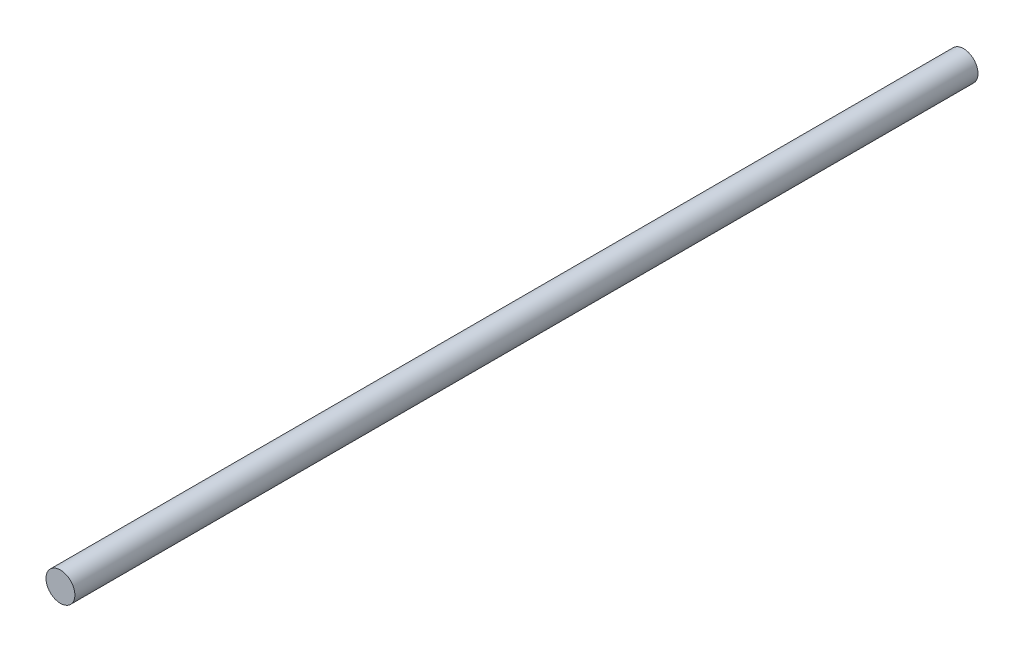
SolidWorks part; units mm, degrees
ref_plane "Front Plane" through (0, 0, 0) normal (0, 0, 1) x (1, 0, 0)
ref_plane "Top Plane" through (0, 0, 0) normal (0, 1, 0) x (1, 0, 0)
ref_plane "Right Plane" through (0, 0, 0) normal (1, 0, 0) x (0, 0, -1)
sketch "Sketch1" plane through (0, 0, 0) normal (0, 1, 0) x (1, 0, 0)
  line L0 (0, -48.7094) -> (0, -46.4499) construction
  line L1 (-4, 0) -> (0, 0)
  line L2 (-4, 0) -> (-4, -250)
  line L3 (-4, -250) -> (0, -250)
  line L4 (0, 0) -> (0, -250)
  dimension "D1" = 8
  dimension "D2" = 250
revolve "Revolve1" add sketch "Sketch1" angle 360 about L0
ref_axis "Axis1" through (0, 0, 63) along (0, 0, -1)
